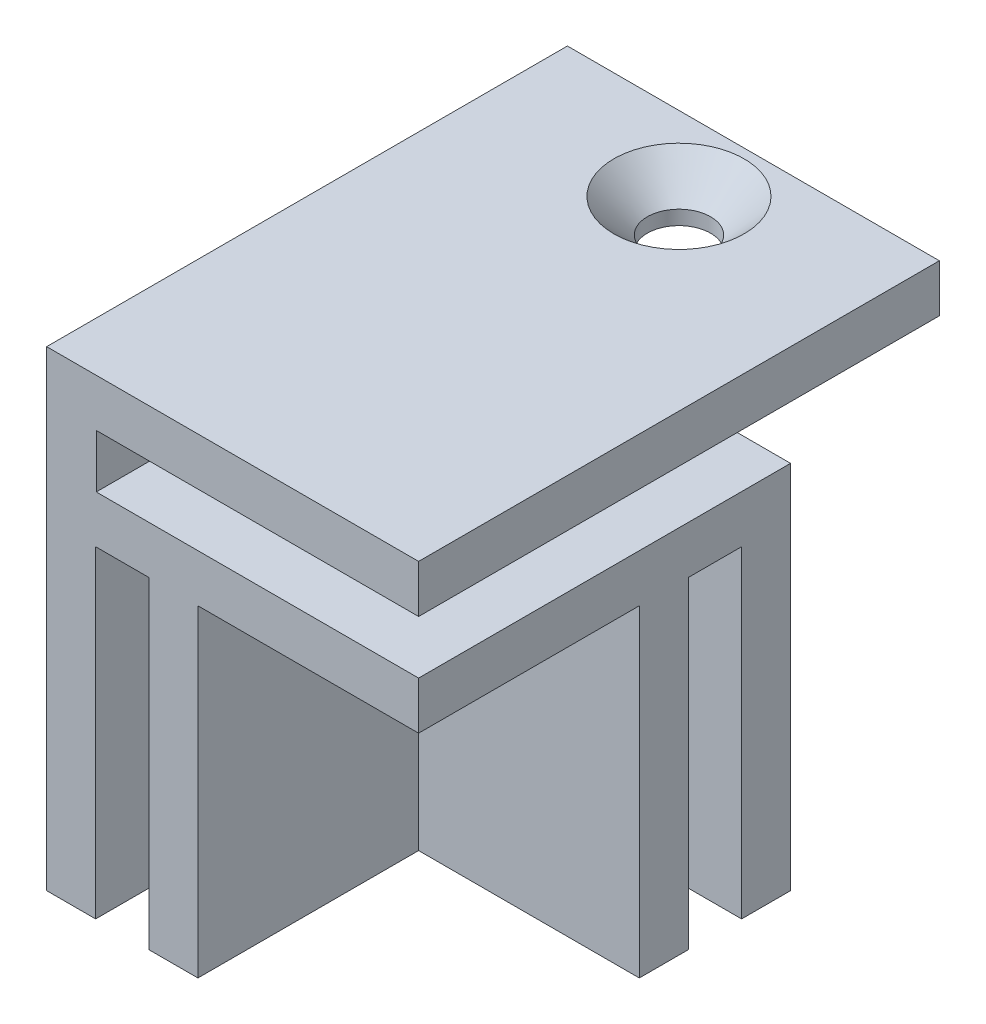
SolidWorks part; units mm, degrees
ref_plane "Plan de face" through (0, 0, 0) normal (0, 0, 1) x (1, 0, 0)
ref_plane "Plan de dessus" through (0, 0, 0) normal (0, 1, 0) x (1, 0, 0)
ref_plane "Plan de droite" through (0, 0, 0) normal (1, 0, 0) x (0, 0, -1)
sketch "Esquisse1" plane through (0, 0, 0) normal (0, 1, 0) x (1, 0, 0)
  line L1 (-35.8867, 13.5315) -> (-5.8867, 13.5315)
  line L2 (-35.8867, 13.5315) -> (-35.8867, -16.4685)
  line L3 (-35.8867, -16.4685) -> (-5.8867, -16.4685)
  line L4 (-5.8867, 13.5315) -> (-5.8867, -16.4685)
  dimension "D1" = 30
  dimension "D2" = 30
extrude "Boss.-Extru.1" add sketch "Esquisse1" along normal blind 38
sketch "Esquisse2" plane through (0, 0, 0) normal (0, -1, 0) x (1, 0, 0)
  line L0 (-5.8867, 16.4685) -> (-5.8867, -13.5315) construction
  line L1 (-5.8867, -9.5815) -> (-23.6867, -9.5815)
  line L2 (-5.8867, -9.5815) -> (-5.8867, -5.2815)
  line L3 (-5.8867, -5.2815) -> (-23.6867, -5.2815)
  line L4 (-23.6867, -9.5815) -> (-23.6867, -5.2815)
  line L5 (-35.8867, 16.4685) -> (-5.8867, 16.4685) construction
  line L6 (-27.6367, 16.4685) -> (-31.9367, 16.4685)
  line L7 (-27.6367, 16.4685) -> (-27.6367, -1.3315)
  line L8 (-27.6367, -1.3315) -> (-31.9367, -1.3315)
  line L9 (-31.9367, 16.4685) -> (-31.9367, -1.3315)
  line L15 (-35.8867, -13.5315) -> (-35.8867, 16.4685) construction
  line L16 (-5.8867, -13.5315) -> (-35.8867, -13.5315) construction
  line L18 (-5.8867, 16.4685) -> (-23.6867, 16.4685)
  line L19 (-5.8867, 16.4685) -> (-5.8867, -1.3315)
  line L20 (-5.8867, -1.3315) -> (-23.6867, -1.3315)
  line L21 (-23.6867, 16.4685) -> (-23.6867, -1.3315)
  dimension "D1" = 4.3
  dimension "D2" = 17.8
  dimension "D3" = 3.95
  dimension "D4" = 4.3
  dimension "D5" = 17.8
  dimension "D6" = 3.95
extrude "Enlèv. mat.-Extru.1" cut sketch "Esquisse2" against normal blind 26
sketch "Esquisse3" plane through (0, 0, 16.4685) normal (0, 0, 1) x (1, 0, 0)
  line L0 (-5.8867, 38) -> (-5.8867, 26) construction
  line L1 (-31.8867, 34.15) -> (-5.8867, 34.15)
  line L2 (-31.8867, 34.15) -> (-31.8867, 29.85)
  line L3 (-31.8867, 29.85) -> (-5.8867, 29.85)
  line L4 (-5.8867, 34.15) -> (-5.8867, 29.85)
  line L5 (-35.8867, 38) -> (-35.8867, 0) construction
  line L6 (-35.8867, 38) -> (-5.8867, 38) construction
  dimension "D1" = 4.3
  dimension "D2" = 4
  dimension "D3" = 3.85
extrude "Enlèv. mat.-Extru.3" cut sketch "Esquisse3" against normal through all
sketch "Esquisse4" plane through (0, 0, -13.5315) normal (0, 0, -1) x (-1, 0, 0)
  line L0 (35.8867, 38) -> (35.8867, 0) construction
  line L1 (5.8867, 38) -> (35.8867, 38)
  line L2 (5.8867, 38) -> (5.8867, 34.15)
  line L3 (5.8867, 34.15) -> (35.8867, 34.15)
  line L4 (35.8867, 38) -> (35.8867, 34.15)
extrude "Boss.-Extru.2" add sketch "Esquisse4" along normal blind 12
sketch "Esquisse7" plane through (0, 38, 0) normal (0, 1, 0) x (1, 0, 0)
  line L0 (-5.8867, -16.4685) -> (-5.8867, 25.5315) construction
  line L1 (-35.8867, 25.5315) -> (-5.8867, 25.5315) construction
  circle A0 centre (-20.8867, 19.5315) radius 5.25
  dimension "D2" = 10.5
  dimension "D1" = 15
  dimension "D3" = 6
hole_wizard "Fraisage pour vis à tête fraisée bombée #51" positions "Esquisse3D2" profile "Esquisse8" countersink size "#5" standard "Ansi Inch" end condition through all
sketch3d "Esquisse3D2"
  point P0 (-20.8867, 38, -19.5315)
sketch "Esquisse8" plane through (-20.8867, 38, -19.5315) normal (1, 0, 0) x (0, 0, 1)
  line L0 (0, 0) -> (0, 38)
  line L1 (0, 38) -> (2.55, 38)
  line L2 (2.55, 38) -> (2.55, 2.7)
  line L3 (2.55, 2.7) -> (5.25, 0)
  line L5 (5.25, 0) -> (0, 0)
  line L6 (-2.55, 2.7) -> (-5.25, 0) construction
  line L11 (0, -6.35) -> (0, 107.95) construction
  dimension "Diamètre du perçage jusqu'au prochain" = 5.1
  dimension "Profondeur du perçage jusqu'au prochain" = 38
  dimension "Diamètre du fraisage entrant" = 10.5
  dimension "Angle du fraisage entrant" = 90
